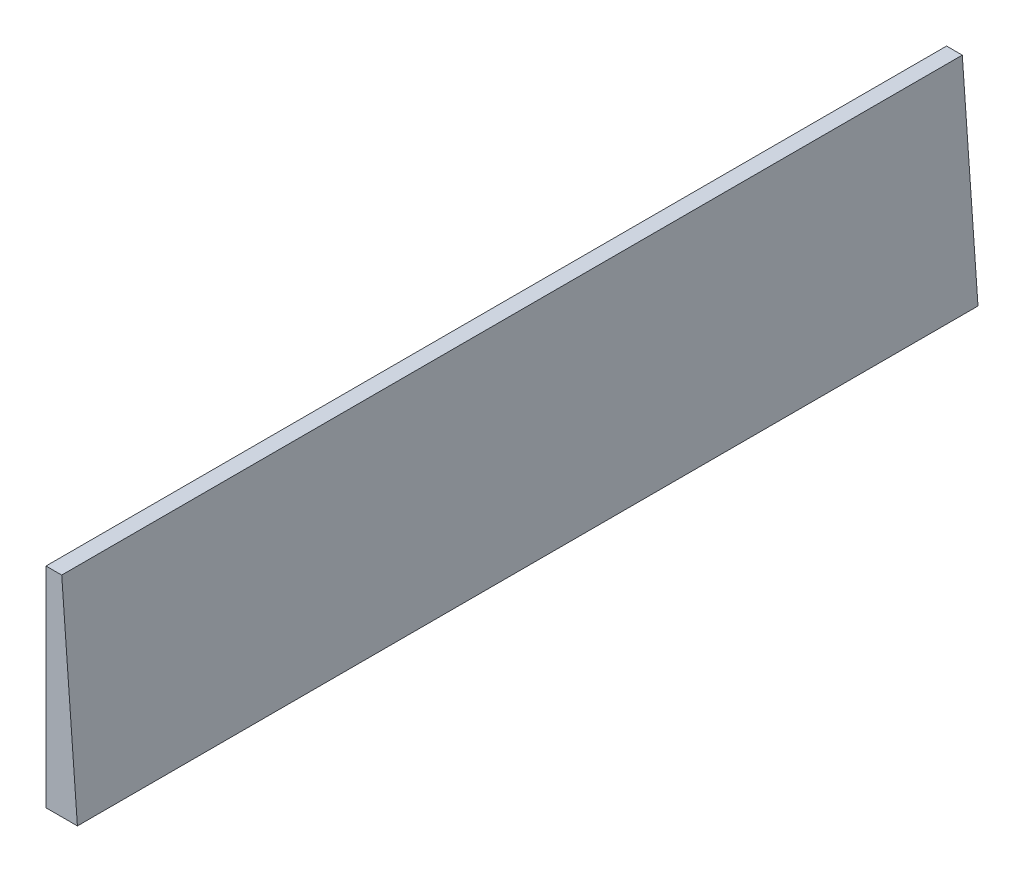
SolidWorks part; units mm, degrees
ref_plane "Front Plane" through (0, 0, 0) normal (0, 0, 1) x (1, 0, 0)
ref_plane "Top Plane" through (0, 0, 0) normal (0, 1, 0) x (1, 0, 0)
ref_plane "Right Plane" through (0, 0, 0) normal (1, 0, 0) x (0, 0, -1)
sketch "Sketch1" plane through (0, 0, 0) normal (0, 0, 1) x (1, 0, 0)
  line L0 (0, 0) -> (0, 1000)
  line L1 (0, 1000) -> (150, 1000)
  line L2 (0, 0) -> (0, -1000)
  line L3 (0, -1000) -> (300, -1000)
  line L4 (300, -1000) -> (150, 1000)
  dimension "D1" = 1000
  dimension "D2" = 150
  dimension "D3" = 300
extrude "Boss-Extrude1" add sketch "Sketch1" along normal blind 4300 and the other way blind 4300
